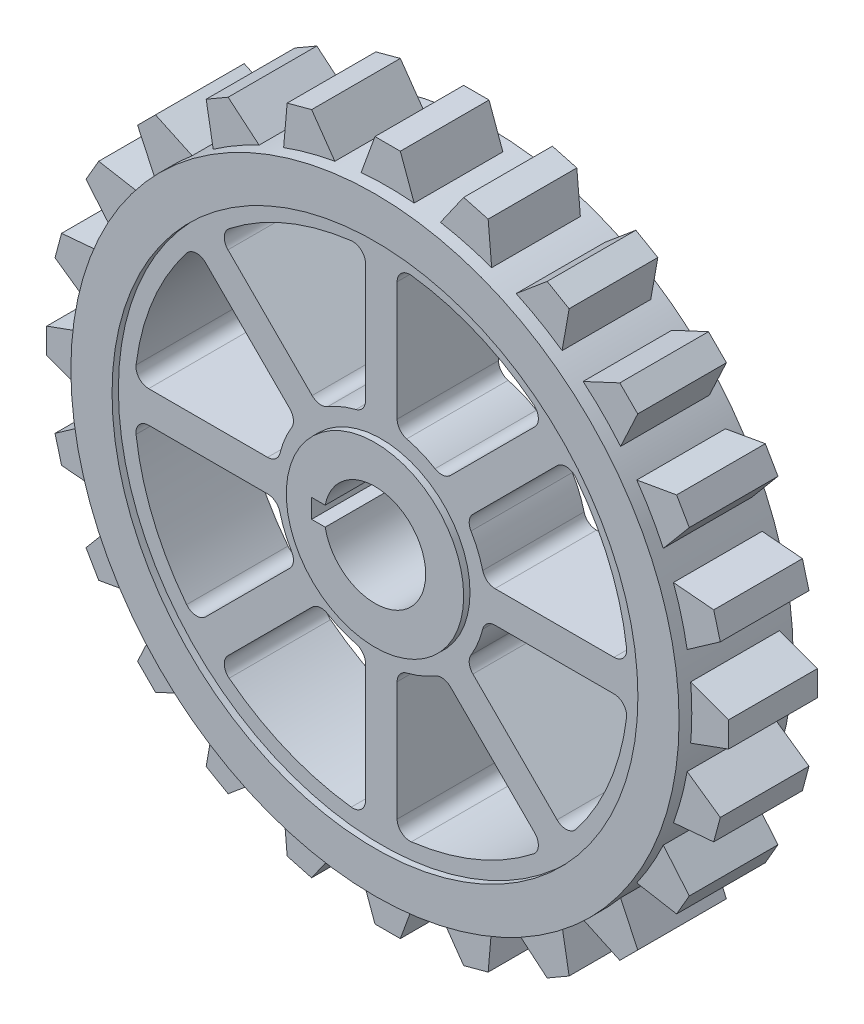
SolidWorks part; units mm, degrees
ref_plane "Front Plane" through (0, 0, 0) normal (1, 0, 0) x (0, 1, 0)
ref_plane "Top Plane" through (0, 0, 0) normal (0, 0, 1) x (0, 1, 0)
ref_plane "Right Plane" through (0, 0, 0) normal (0, 1, 0) x (-1, 0, 0)
sketch "Sketch2" plane through (0, 0, 0) normal (0, 0, 1) x (0, 1, 0)
  line L0 (0, 0) -> (0, 80.6478) construction
  line L1 (-4.1838, 47.8173) -> (-2, 53.8173)
  line L2 (-2, 53.8173) -> (2, 53.8173)
  line L3 (2, 53.8173) -> (4.1838, 47.8173)
  line L4 (15.8608, 51.4659) -> (16.4173, 45.1051)
  line L5 (11.9971, 52.5012) -> (15.8608, 51.4659)
  line L6 (8.3348, 47.2708) -> (11.9971, 52.5012)
  line L7 (28.6407, 45.6072) -> (27.532, 39.3191)
  line L8 (25.1766, 47.6072) -> (28.6407, 45.6072)
  line L9 (20.2854, 43.5029) -> (25.1766, 47.6072)
  line L10 (39.4688, 36.6404) -> (36.7704, 30.8535)
  line L11 (36.6404, 39.4688) -> (39.4688, 36.6404)
  line L12 (30.8535, 36.7704) -> (36.6404, 39.4688)
  line L13 (47.6072, 25.1766) -> (43.5029, 20.2854)
  line L14 (45.6072, 28.6407) -> (47.6072, 25.1766)
  line L15 (39.3191, 27.532) -> (45.6072, 28.6407)
  line L16 (52.5012, 11.9971) -> (47.2708, 8.3348)
  line L17 (51.4659, 15.8608) -> (52.5012, 11.9971)
  line L18 (45.1051, 16.4173) -> (51.4659, 15.8608)
  line L19 (53.8173, -2) -> (47.8173, -4.1838)
  line L20 (53.8173, 2) -> (53.8173, -2)
  line L21 (47.8173, 4.1838) -> (53.8173, 2)
  line L22 (51.4659, -15.8608) -> (45.1051, -16.4173)
  line L23 (52.5012, -11.9971) -> (51.4659, -15.8608)
  line L24 (47.2708, -8.3348) -> (52.5012, -11.9971)
  line L25 (45.6072, -28.6407) -> (39.3191, -27.532)
  line L26 (47.6072, -25.1766) -> (45.6072, -28.6407)
  line L27 (43.5029, -20.2854) -> (47.6072, -25.1766)
  line L28 (36.6404, -39.4688) -> (30.8535, -36.7704)
  line L29 (39.4688, -36.6404) -> (36.6404, -39.4688)
  line L30 (36.7704, -30.8535) -> (39.4688, -36.6404)
  line L31 (25.1766, -47.6072) -> (20.2854, -43.5029)
  line L32 (28.6407, -45.6072) -> (25.1766, -47.6072)
  line L33 (27.532, -39.3191) -> (28.6407, -45.6072)
  line L34 (11.9971, -52.5012) -> (8.3348, -47.2708)
  line L35 (15.8608, -51.4659) -> (11.9971, -52.5012)
  line L36 (16.4173, -45.1051) -> (15.8608, -51.4659)
  line L37 (-2, -53.8173) -> (-4.1838, -47.8173)
  line L38 (2, -53.8173) -> (-2, -53.8173)
  line L39 (4.1838, -47.8173) -> (2, -53.8173)
  line L40 (-15.8608, -51.4659) -> (-16.4173, -45.1051)
  line L41 (-11.9971, -52.5012) -> (-15.8608, -51.4659)
  line L42 (-8.3348, -47.2708) -> (-11.9971, -52.5012)
  line L43 (-28.6407, -45.6072) -> (-27.532, -39.3191)
  line L44 (-25.1766, -47.6072) -> (-28.6407, -45.6072)
  line L45 (-20.2854, -43.5029) -> (-25.1766, -47.6072)
  line L46 (-39.4688, -36.6404) -> (-36.7704, -30.8535)
  line L47 (-36.6404, -39.4688) -> (-39.4688, -36.6404)
  line L48 (-30.8535, -36.7704) -> (-36.6404, -39.4688)
  line L49 (-47.6072, -25.1766) -> (-43.5029, -20.2854)
  line L50 (-45.6072, -28.6407) -> (-47.6072, -25.1766)
  line L51 (-39.3191, -27.532) -> (-45.6072, -28.6407)
  line L52 (-52.5012, -11.9971) -> (-47.2708, -8.3348)
  line L53 (-51.4659, -15.8608) -> (-52.5012, -11.9971)
  line L54 (-45.1051, -16.4173) -> (-51.4659, -15.8608)
  line L55 (-53.8173, 2) -> (-47.8173, 4.1838)
  line L56 (-53.8173, -2) -> (-53.8173, 2)
  line L57 (-47.8173, -4.1838) -> (-53.8173, -2)
  line L58 (-51.4659, 15.8608) -> (-45.1051, 16.4173)
  line L59 (-52.5012, 11.9971) -> (-51.4659, 15.8608)
  line L60 (-47.2708, 8.3348) -> (-52.5012, 11.9971)
  line L61 (-45.6072, 28.6407) -> (-39.3191, 27.532)
  line L62 (-47.6072, 25.1766) -> (-45.6072, 28.6407)
  line L63 (-43.5029, 20.2854) -> (-47.6072, 25.1766)
  line L64 (-36.6404, 39.4688) -> (-30.8535, 36.7704)
  line L65 (-39.4688, 36.6404) -> (-36.6404, 39.4688)
  line L66 (-36.7704, 30.8535) -> (-39.4688, 36.6404)
  line L67 (-25.1766, 47.6072) -> (-20.2854, 43.5029)
  line L68 (-28.6407, 45.6072) -> (-25.1766, 47.6072)
  line L69 (-27.532, 39.3191) -> (-28.6407, 45.6072)
  line L70 (-11.9971, 52.5012) -> (-8.3348, 47.2708)
  line L71 (-15.8608, 51.4659) -> (-11.9971, 52.5012)
  line L72 (-16.4173, 45.1051) -> (-15.8608, 51.4659)
  arc A0 (-4.1838, 47.8173) -> (-8.3348, 47.2708) centre (0, 0) ccw
  circle A1 centre (0, 0) radius 41.5
  arc A2 (-16.4173, 45.1051) -> (-20.2854, 43.5029) centre (0, 0) ccw
  arc A3 (-27.532, 39.3191) -> (-30.8535, 36.7704) centre (0, 0) ccw
  arc A4 (-36.7704, 30.8535) -> (-39.3191, 27.532) centre (0, 0) ccw
  arc A5 (8.3348, 47.2708) -> (4.1838, 47.8173) centre (0, 0) ccw
  arc A6 (20.2854, 43.5029) -> (16.4173, 45.1051) centre (0, 0) ccw
  arc A7 (30.8535, 36.7704) -> (27.532, 39.3191) centre (0, 0) ccw
  arc A8 (39.3191, 27.532) -> (36.7704, 30.8535) centre (0, 0) ccw
  arc A9 (45.1051, 16.4173) -> (43.5029, 20.2854) centre (0, 0) ccw
  arc A10 (47.8173, 4.1838) -> (47.2708, 8.3348) centre (0, 0) ccw
  arc A11 (47.2708, -8.3348) -> (47.8173, -4.1838) centre (0, 0) ccw
  arc A12 (43.5029, -20.2854) -> (45.1051, -16.4173) centre (0, 0) ccw
  arc A13 (36.7704, -30.8535) -> (39.3191, -27.532) centre (0, 0) ccw
  arc A14 (27.532, -39.3191) -> (30.8535, -36.7704) centre (0, 0) ccw
  arc A15 (16.4173, -45.1051) -> (20.2854, -43.5029) centre (0, 0) ccw
  arc A16 (4.1838, -47.8173) -> (8.3348, -47.2708) centre (0, 0) ccw
  arc A17 (-8.3348, -47.2708) -> (-4.1838, -47.8173) centre (0, 0) ccw
  arc A18 (-20.2854, -43.5029) -> (-16.4173, -45.1051) centre (0, 0) ccw
  arc A19 (-30.8535, -36.7704) -> (-27.532, -39.3191) centre (0, 0) ccw
  arc A20 (-39.3191, -27.532) -> (-36.7704, -30.8535) centre (0, 0) ccw
  arc A21 (-45.1051, -16.4173) -> (-43.5029, -20.2854) centre (0, 0) ccw
  arc A22 (-47.8173, -4.1838) -> (-47.2708, -8.3348) centre (0, 0) ccw
  arc A23 (-47.2708, 8.3348) -> (-47.8173, 4.1838) centre (0, 0) ccw
  arc A24 (-43.5029, 20.2854) -> (-45.1051, 16.4173) centre (0, 0) ccw
  point P7 (0, 53.8173)
  point P104 (0, 0)
  dimension "D1" = 96
  dimension "D2" = 6.5
  dimension "D3" = 40
  dimension "D4" = 6
  dimension "D5" = 4
  dimension "D6" = 24
extrude "Boss-Extrude2" add sketch "Sketch2" along normal blind 18
sketch "Sketch4" plane through (0, 0, 0) normal (0, 0, 1) x (0, 1, 0)
  circle A1 centre (0, 0) radius 41.5
  point P7 (0, 10)
  dimension "D2" = 83
extrude "Boss-Extrude3" add sketch "Sketch4" along normal mid plane 16 from offset 9
sketch "Sketch5" plane through (0, 0, 0) normal (0, 0, 1) x (0, 1, 0)
  circle A0 centre (0, 0) radius 14
  dimension "D1" = 28
extrude "Boss-Extrude4" add sketch "Sketch5" along normal blind 18
sketch "Sketch6" plane through (0, 0, 0) normal (0, 0, 1) x (0, 1, 0)
  line L0 (-4.1838, 47.8173) -> (-2, 53.8173)
  line L1 (-2, 53.8173) -> (2, 53.8173)
  line L2 (2, 53.8173) -> (4.1838, 47.8173)
  line L3 (8.3348, 47.2708) -> (11.9971, 52.5012)
  line L4 (11.9971, 52.5012) -> (15.8608, 51.4659)
  line L5 (15.8608, 51.4659) -> (16.4173, 45.1051)
  line L6 (20.2854, 43.5029) -> (25.1766, 47.6072)
  line L7 (25.1766, 47.6072) -> (28.6407, 45.6072)
  line L8 (28.6407, 45.6072) -> (27.532, 39.3191)
  line L9 (30.8535, 36.7704) -> (36.6404, 39.4688)
  line L10 (36.6404, 39.4688) -> (39.4688, 36.6404)
  line L11 (39.4688, 36.6404) -> (36.7704, 30.8535)
  line L12 (39.3191, 27.532) -> (45.6072, 28.6407)
  line L13 (45.6072, 28.6407) -> (47.6072, 25.1766)
  line L14 (47.6072, 25.1766) -> (43.5029, 20.2854)
  line L15 (45.1051, 16.4173) -> (51.4659, 15.8608)
  line L16 (51.4659, 15.8608) -> (52.5012, 11.9971)
  line L17 (52.5012, 11.9971) -> (47.2708, 8.3348)
  line L18 (47.8173, 4.1838) -> (53.8173, 2)
  line L19 (53.8173, 2) -> (53.8173, -2)
  line L20 (53.8173, -2) -> (47.8173, -4.1838)
  line L21 (47.2708, -8.3348) -> (52.5012, -11.9971)
  line L22 (52.5012, -11.9971) -> (51.4659, -15.8608)
  line L23 (51.4659, -15.8608) -> (45.1051, -16.4173)
  line L24 (43.5029, -20.2854) -> (47.6072, -25.1766)
  line L25 (47.6072, -25.1766) -> (45.6072, -28.6407)
  line L26 (45.6072, -28.6407) -> (39.3191, -27.532)
  line L27 (36.7704, -30.8535) -> (39.4688, -36.6404)
  line L28 (39.4688, -36.6404) -> (36.6404, -39.4688)
  line L29 (36.6404, -39.4688) -> (30.8535, -36.7704)
  line L30 (27.532, -39.3191) -> (28.6407, -45.6072)
  line L31 (28.6407, -45.6072) -> (25.1766, -47.6072)
  line L32 (25.1766, -47.6072) -> (20.2854, -43.5029)
  line L33 (16.4173, -45.1051) -> (15.8608, -51.4659)
  line L34 (15.8608, -51.4659) -> (11.9971, -52.5012)
  line L35 (11.9971, -52.5012) -> (8.3348, -47.2708)
  line L36 (4.1838, -47.8173) -> (2, -53.8173)
  line L37 (2, -53.8173) -> (-2, -53.8173)
  line L38 (-2, -53.8173) -> (-4.1838, -47.8173)
  line L39 (-8.3348, -47.2708) -> (-11.9971, -52.5012)
  line L40 (-11.9971, -52.5012) -> (-15.8608, -51.4659)
  line L41 (-15.8608, -51.4659) -> (-16.4173, -45.1051)
  line L42 (-20.2854, -43.5029) -> (-25.1766, -47.6072)
  line L43 (-25.1766, -47.6072) -> (-28.6407, -45.6072)
  line L44 (-28.6407, -45.6072) -> (-27.532, -39.3191)
  line L45 (-30.8535, -36.7704) -> (-36.6404, -39.4688)
  line L46 (-36.6404, -39.4688) -> (-39.4688, -36.6404)
  line L47 (-39.4688, -36.6404) -> (-36.7704, -30.8535)
  line L48 (-39.3191, -27.532) -> (-45.6072, -28.6407)
  line L49 (-45.6072, -28.6407) -> (-47.6072, -25.1766)
  line L50 (-47.6072, -25.1766) -> (-43.5029, -20.2854)
  line L51 (-45.1051, -16.4173) -> (-51.4659, -15.8608)
  line L52 (-51.4659, -15.8608) -> (-52.5012, -11.9971)
  line L53 (-52.5012, -11.9971) -> (-47.2708, -8.3348)
  line L54 (-47.8173, -4.1838) -> (-53.8173, -2)
  line L55 (-53.8173, -2) -> (-53.8173, 2)
  line L56 (-53.8173, 2) -> (-47.8173, 4.1838)
  line L57 (-47.2708, 8.3348) -> (-52.5012, 11.9971)
  line L58 (-52.5012, 11.9971) -> (-51.4659, 15.8608)
  line L59 (-51.4659, 15.8608) -> (-45.1051, 16.4173)
  line L60 (-43.5029, 20.2854) -> (-47.6072, 25.1766)
  line L61 (-47.6072, 25.1766) -> (-45.6072, 28.6407)
  line L62 (-45.6072, 28.6407) -> (-39.3191, 27.532)
  line L63 (-36.7704, 30.8535) -> (-39.4688, 36.6404)
  line L64 (-39.4688, 36.6404) -> (-36.6404, 39.4688)
  line L65 (-36.6404, 39.4688) -> (-30.8535, 36.7704)
  line L66 (-27.532, 39.3191) -> (-28.6407, 45.6072)
  line L67 (-28.6407, 45.6072) -> (-25.1766, 47.6072)
  line L68 (-25.1766, 47.6072) -> (-20.2854, 43.5029)
  line L69 (-16.4173, 45.1051) -> (-15.8608, 51.4659)
  line L70 (-15.8608, 51.4659) -> (-11.9971, 52.5012)
  line L71 (-11.9971, 52.5012) -> (-8.3348, 47.2708)
  arc A0 (-4.1838, 47.8173) -> (4.1838, 47.8173) centre (0, 0) cw
  arc A1 (8.3348, 47.2708) -> (16.4173, 45.1051) centre (0, 0) cw
  arc A2 (20.2854, 43.5029) -> (27.532, 39.3191) centre (0, 0) cw
  arc A3 (30.8535, 36.7704) -> (36.7704, 30.8535) centre (0, 0) cw
  arc A4 (39.3191, 27.532) -> (43.5029, 20.2854) centre (0, 0) cw
  arc A5 (45.1051, 16.4173) -> (47.2708, 8.3348) centre (0, 0) cw
  arc A6 (47.8173, 4.1838) -> (47.8173, -4.1838) centre (0, 0) cw
  arc A7 (47.2708, -8.3348) -> (45.1051, -16.4173) centre (0, 0) cw
  arc A8 (43.5029, -20.2854) -> (39.3191, -27.532) centre (0, 0) cw
  arc A9 (36.7704, -30.8535) -> (30.8535, -36.7704) centre (0, 0) cw
  arc A10 (27.532, -39.3191) -> (20.2854, -43.5029) centre (0, 0) cw
  arc A11 (16.4173, -45.1051) -> (8.3348, -47.2708) centre (0, 0) cw
  arc A12 (4.1838, -47.8173) -> (-4.1838, -47.8173) centre (0, 0) cw
  arc A13 (-8.3348, -47.2708) -> (-16.4173, -45.1051) centre (0, 0) cw
  arc A14 (-20.2854, -43.5029) -> (-27.532, -39.3191) centre (0, 0) cw
  arc A15 (-30.8535, -36.7704) -> (-36.7704, -30.8535) centre (0, 0) cw
  arc A16 (-39.3191, -27.532) -> (-43.5029, -20.2854) centre (0, 0) cw
  arc A17 (-45.1051, -16.4173) -> (-47.2708, -8.3348) centre (0, 0) cw
  arc A18 (-47.8173, -4.1838) -> (-47.8173, 4.1838) centre (0, 0) cw
  arc A19 (-47.2708, 8.3348) -> (-45.1051, 16.4173) centre (0, 0) cw
  arc A20 (-43.5029, 20.2854) -> (-39.3191, 27.532) centre (0, 0) cw
  arc A21 (-36.7704, 30.8535) -> (-30.8535, 36.7704) centre (0, 0) cw
  arc A22 (-27.532, 39.3191) -> (-20.2854, 43.5029) centre (0, 0) cw
  arc A23 (-16.4173, 45.1051) -> (-8.3348, 47.2708) centre (0, 0) cw
  point P104 (0, 0)
  dimension "D1" = 48
  dimension "D2" = 24
extrude "Cut-Extrude2" cut sketch "Sketch6" against normal blind 2 from surface starting at face at (0, 0, 18)
extrude "Cut-Extrude3" cut sketch "Sketch6<2>" along normal blind 2
sketch "Sketch6<2>" plane through (0, 0, 0) normal (0, 0, 1) x (0, 1, 0) same geometry as "Sketch6"
sketch "Sketch7" plane through (0, 0, 0) normal (0, 0, 1) x (0, 1, 0)
  line L0 (0, 0) -> (0, 20) construction
  line L1 (-1.5, 7.8581) -> (-1.5, 10)
  line L2 (-1.5, 10) -> (1.5, 10)
  line L3 (1.5, 10) -> (1.5, 7.8581)
  arc A0 (-1.5, 7.8581) -> (1.5, 7.8581) centre (0, 0) ccw
  point P6 (0, 10)
  dimension "D1" = 16
  dimension "D2" = 3
  dimension "D3" = 10
extrude "Cut-Extrude4" cut sketch "Sketch7" along normal blind 18
sketch "Sketch8" plane through (0, 0, 0) normal (0, 0, 1) x (0, 1, 0)
  line L0 (0, 0) -> (0, 45.9616) construction
  line L1 (2.5, 36.7253) -> (2.5, 17.9444)
  line L2 (24.201, 27.7365) -> (10.9208, 14.4563)
  line L3 (0, 0) -> (42.17, 42.17) construction
  line L4 (0, 0) -> (62, 0) construction
  line L5 (27.7365, 24.201) -> (14.4563, 10.9208)
  line L6 (36.7253, 2.5) -> (17.9444, 2.5)
  line L7 (36.7253, -2.5) -> (17.9444, -2.5)
  line L8 (27.7365, -24.201) -> (14.4563, -10.9208)
  line L9 (24.201, -27.7365) -> (10.9208, -14.4563)
  line L10 (2.5, -36.7253) -> (2.5, -17.9444)
  line L11 (-2.5, -36.7253) -> (-2.5, -17.9444)
  line L12 (-24.201, -27.7365) -> (-10.9208, -14.4563)
  line L13 (-27.7365, -24.201) -> (-14.4563, -10.9208)
  line L14 (-36.7253, -2.5) -> (-17.9444, -2.5)
  line L15 (-36.7253, 2.5) -> (-17.9444, 2.5)
  line L16 (-27.7365, 24.201) -> (-14.4563, 10.9208)
  line L17 (-24.201, 27.7365) -> (-10.9208, 14.4563)
  line L18 (-2.5, 36.7253) -> (-2.5, 17.9444)
  arc A0 (4.7432, 38.7105) -> (24.0185, 30.7264) centre (0, 0) cw
  arc A1 (4.0135, 16.0044) -> (8.4789, 14.1548) centre (0, 0) cw
  arc A2 (4.7432, 38.7105) -> (2.5, 36.7253) centre (4.5, 36.7253) ccw
  arc A3 (4.0135, 16.0044) -> (2.5, 17.9444) centre (4.5, 17.9444) cw
  arc A4 (8.4789, 14.1548) -> (10.9208, 14.4563) centre (9.5066, 15.8706) ccw
  arc A5 (24.0185, 30.7264) -> (24.201, 27.7365) centre (22.7868, 29.1507) cw
  arc A6 (30.7264, 24.0185) -> (38.7105, 4.7432) centre (0, 0) cw
  arc A7 (30.7264, 24.0185) -> (27.7365, 24.201) centre (29.1507, 22.7868) ccw
  arc A8 (14.1548, 8.4789) -> (14.4563, 10.9208) centre (15.8706, 9.5066) cw
  arc A9 (14.1548, 8.4789) -> (16.0044, 4.0135) centre (0, 0) cw
  arc A10 (16.0044, 4.0135) -> (17.9444, 2.5) centre (17.9444, 4.5) ccw
  arc A11 (38.7105, 4.7432) -> (36.7253, 2.5) centre (36.7253, 4.5) cw
  arc A12 (38.7105, -4.7432) -> (30.7264, -24.0185) centre (0, 0) cw
  arc A13 (38.7105, -4.7432) -> (36.7253, -2.5) centre (36.7253, -4.5) ccw
  arc A14 (16.0044, -4.0135) -> (17.9444, -2.5) centre (17.9444, -4.5) cw
  arc A15 (16.0044, -4.0135) -> (14.1548, -8.4789) centre (0, 0) cw
  arc A16 (14.1548, -8.4789) -> (14.4563, -10.9208) centre (15.8706, -9.5066) ccw
  arc A17 (30.7264, -24.0185) -> (27.7365, -24.201) centre (29.1507, -22.7868) cw
  arc A18 (24.0185, -30.7264) -> (4.7432, -38.7105) centre (0, 0) cw
  arc A19 (24.0185, -30.7264) -> (24.201, -27.7365) centre (22.7868, -29.1507) ccw
  arc A20 (8.4789, -14.1548) -> (10.9208, -14.4563) centre (9.5066, -15.8706) cw
  arc A21 (8.4789, -14.1548) -> (4.0135, -16.0044) centre (0, 0) cw
  arc A22 (4.0135, -16.0044) -> (2.5, -17.9444) centre (4.5, -17.9444) ccw
  arc A23 (4.7432, -38.7105) -> (2.5, -36.7253) centre (4.5, -36.7253) cw
  arc A24 (-4.7432, -38.7105) -> (-24.0185, -30.7264) centre (0, 0) cw
  arc A25 (-4.7432, -38.7105) -> (-2.5, -36.7253) centre (-4.5, -36.7253) ccw
  arc A26 (-4.0135, -16.0044) -> (-2.5, -17.9444) centre (-4.5, -17.9444) cw
  arc A27 (-4.0135, -16.0044) -> (-8.4789, -14.1548) centre (0, 0) cw
  arc A28 (-8.4789, -14.1548) -> (-10.9208, -14.4563) centre (-9.5066, -15.8706) ccw
  arc A29 (-24.0185, -30.7264) -> (-24.201, -27.7365) centre (-22.7868, -29.1507) cw
  arc A30 (-30.7264, -24.0185) -> (-38.7105, -4.7432) centre (0, 0) cw
  arc A31 (-30.7264, -24.0185) -> (-27.7365, -24.201) centre (-29.1507, -22.7868) ccw
  arc A32 (-14.1548, -8.4789) -> (-14.4563, -10.9208) centre (-15.8706, -9.5066) cw
  arc A33 (-14.1548, -8.4789) -> (-16.0044, -4.0135) centre (0, 0) cw
  arc A34 (-16.0044, -4.0135) -> (-17.9444, -2.5) centre (-17.9444, -4.5) ccw
  arc A35 (-38.7105, -4.7432) -> (-36.7253, -2.5) centre (-36.7253, -4.5) cw
  arc A36 (-38.7105, 4.7432) -> (-30.7264, 24.0185) centre (0, 0) cw
  arc A37 (-38.7105, 4.7432) -> (-36.7253, 2.5) centre (-36.7253, 4.5) ccw
  arc A38 (-16.0044, 4.0135) -> (-17.9444, 2.5) centre (-17.9444, 4.5) cw
  arc A39 (-16.0044, 4.0135) -> (-14.1548, 8.4789) centre (0, 0) cw
  arc A40 (-14.1548, 8.4789) -> (-14.4563, 10.9208) centre (-15.8706, 9.5066) ccw
  arc A41 (-30.7264, 24.0185) -> (-27.7365, 24.201) centre (-29.1507, 22.7868) cw
  arc A42 (-24.0185, 30.7264) -> (-4.7432, 38.7105) centre (0, 0) cw
  arc A43 (-24.0185, 30.7264) -> (-24.201, 27.7365) centre (-22.7868, 29.1507) ccw
  arc A44 (-8.4789, 14.1548) -> (-10.9208, 14.4563) centre (-9.5066, 15.8706) cw
  arc A45 (-8.4789, 14.1548) -> (-4.0135, 16.0044) centre (0, 0) cw
  arc A46 (-4.0135, 16.0044) -> (-2.5, 17.9444) centre (-4.5, 17.9444) ccw
  arc A47 (-4.7432, 38.7105) -> (-2.5, 36.7253) centre (-4.5, 36.7253) cw
  point P104 (0, 0)
  dimension "D1" = 39
  dimension "D2" = 16.5
  dimension "D3" = 2
  dimension "D4" = 2
  dimension "D5" = 2
  dimension "D6" = 2
  dimension "D7" = 2.5
  dimension "D8" = 45
  dimension "D9" = 2.5
  dimension "D10" = 8
extrude "Cut-Extrude5" cut sketch "Sketch8" along normal blind 18
